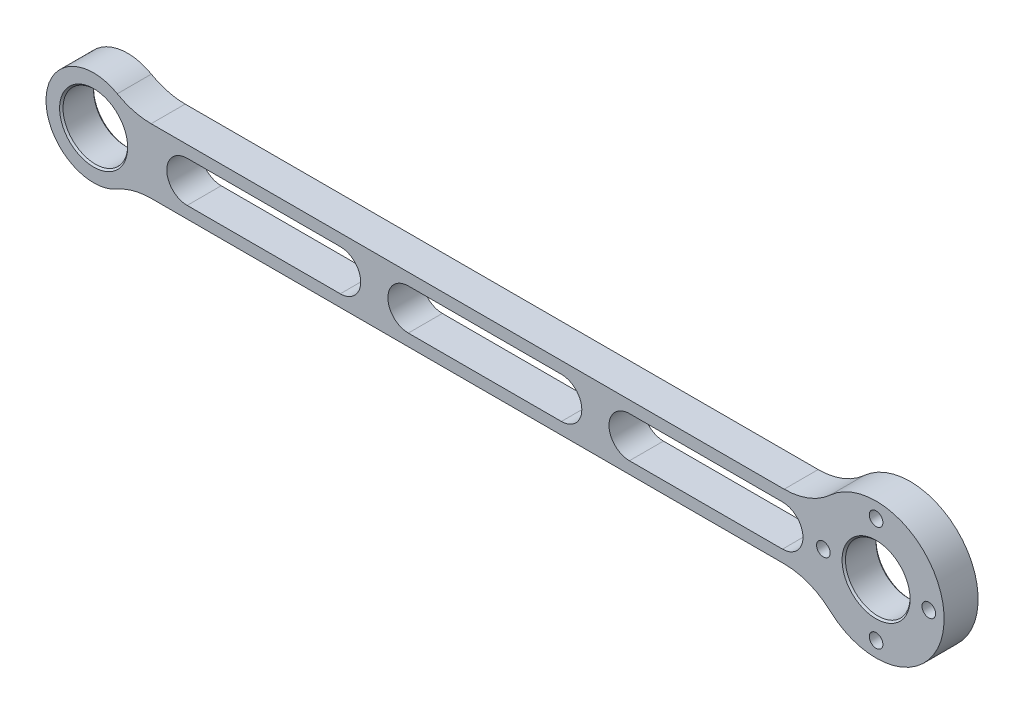
SolidWorks part; units mm, degrees
ref_plane "前视基准面" through (0, 0, 0) normal (0, 0, 1) x (1, 0, 0)
ref_plane "上视基准面" through (0, 0, 0) normal (0, 1, 0) x (1, 0, 0)
ref_plane "右视基准面" through (0, 0, 0) normal (1, 0, 0) x (0, 0, -1)
sketch "草图1" plane through (0, 0, 0) normal (0, 0, 1) x (1, 0, 0)
  line L0 (0, 0) -> (230, 0) construction
  line L1 (1.5589, 9.3712) -> (0, 9.5) construction
  line L2 (202.9861, -9.5) -> (20.8216, -9.5)
  line L4 (202.9861, 9.5) -> (21.6386, 9.5)
  line L6 (230, -9.5) -> (228.4411, -9.3712) construction
  line L7 (230, 9.5) -> (228.4411, 9.3712) construction
  line L8 (1.5589, -9.3712) -> (0, -9.5) construction
  line L9 (20.8216, -9.5) -> (16.9041, -9.5)
  line L10 (21.6386, 9.5) -> (16.9041, 9.5)
  circle A0 centre (0, 0) radius 9.5
  arc A1 (-0.2295, 13.9981) -> (3.4233, -13.575) centre (0, 0) ccw
  circle A2 centre (230, 0) radius 9.5
  arc A3 (214.8013, -13) -> (214.8013, 13) centre (230, 0) ccw
  arc A7 (6.9605, 12.1471) -> (6.9605, -12.1471) centre (0, 0) ccw
  arc A8 (6.9605, -12.1471) -> (16.9041, -9.5) centre (16.9041, -29.5) cw
  arc A9 (6.9605, 12.1471) -> (16.9041, 9.5) centre (16.9041, 29.5) ccw
  arc A10 (216.4931, -14.75) -> (216.4931, 14.75) centre (230, 0) ccw
  arc A11 (202.9861, -9.5) -> (216.4931, -14.75) centre (202.9861, -29.5) cw
  arc A12 (216.4931, 14.75) -> (202.9861, 9.5) centre (202.9861, 29.5) cw
  point P7 (115, 0)
  dimension "D1" = 19
  dimension "D2" = 28
  dimension "D3" = 20
  dimension "D4" = 19
  dimension "D5" = 20
  dimension "D8" = 20
  dimension "D6" = 9.5
  dimension "D7" = 9.5
extrude "凸台-拉伸2" add sketch "草图1" along normal blind 10 contours A1 L2 A3 L4 A2 A0 region at (127.347, 0, 0)
chamfer "倒角1" distance 0.5 angle 45 2 edges at (9.5, 0, 10) (9.5, 0, 0)
sketch "草图2" plane through (0, 0, 10) normal (0, 0, 1) x (1, 0, 0)
  line L0 (0, 0) -> (21.5, 0) construction
  line L1 (115, -1.5) -> (115, 9.5) construction
  line L2 (202.9861, 9.5) -> (16.9041, 9.5) construction
  line L3 (115, -1.5) -> (137.5, -6) construction
  line L4 (92.5, -6) -> (137.5, -6)
  line L6 (92.5, 6) -> (137.5, 6)
  line L8 (115, -1.5) -> (135.7692, 2.6538) construction
  line L10 (157.5, -6) -> (202.5, -6)
  line L12 (157.5, 6) -> (202.5, 6)
  line L16 (27.5, -6) -> (72.5, -6)
  line L18 (27.5, 6) -> (72.5, 6)
  line L20 (29.2308, -4.1538) -> (50, 0) construction
  line L21 (50, 0) -> (157.5, 0) construction
  line L22 (162, 0) -> (230, 0) construction
  arc A1 (27.5, 6) -> (27.5, -6) centre (27.5, 0) ccw
  arc A2 (92.5, 6) -> (92.5, -6) centre (92.5, 0) ccw
  arc A3 (137.5, -6) -> (137.5, 6) centre (137.5, 0) ccw
  arc A4 (157.5, 6) -> (157.5, -6) centre (157.5, 0) ccw
  arc A6 (72.5, -6) -> (72.5, 6) centre (72.5, 0) ccw
  arc A7 (202.5, -6) -> (202.5, 6) centre (202.5, 0) ccw
  point P12 (180, 0)
  point P17 (50, 0)
  dimension "D1" = 12
  dimension "D2" = 12
  dimension "D3" = 45
  dimension "D4" = 45
  dimension "D5" = 45
  dimension "D6" = 12
extrude "切除-拉伸1" cut sketch "草图2" against normal blind 10
sketch "草图3" plane through (0, 0, 10) normal (0, 0, 1) x (1, 0, 0)
  line L0 (230, 0) -> (243, 0) construction
  line L1 (230, 0) -> (236.5, 11.2583) construction
  line L2 (230, 0) -> (223.5, 11.2583) construction
  arc A8 (220.8385, 11.8771) -> (215.1333, 1.9956) centre (230, 0) ccw
  circle A9 centre (215, 0) radius 2
  circle A12 centre (245, 0) radius 2
  circle A13 centre (237.5, 12.9904) radius 2
  circle A14 centre (222.5, 12.9904) radius 2
  arc A15 (235.7051, 13.8727) -> (224.2949, 13.8727) centre (230, 0) ccw
  arc A16 (244.8667, 1.9956) -> (239.1615, 11.8771) centre (230, 0) ccw
  arc A17 (215.1333, -1.9956) -> (220.8385, -11.8771) centre (230, 0) ccw
  circle A18 centre (237.5, -12.9904) radius 2
  circle A19 centre (222.5, -12.9904) radius 2
  arc A20 (224.2949, -13.8727) -> (235.7051, -13.8727) centre (230, 0) ccw
  arc A21 (239.1615, -11.8771) -> (244.8667, -1.9956) centre (230, 0) ccw
  point P18 (230, 0)
  dimension "D1" = 60
  dimension "D2" = 60
extrude "切除-拉伸2" cut sketch "草图3" against normal blind 10 contours A12 | A14 | A13 region at (222.5, 12.9904, 10) region at (237.5, 12.9904, 10) region at (245, 0, 10)
chamfer "倒角2" distance 0.5 angle 45 1 edges at (239.5, 0, 10)
sketch "草图5" plane through (0, 0, 10) normal (0, 0, 1) x (1, 0, 0)
  line L0 (230, 0) -> (222.5, 12.9904) construction
  line L1 (230, 0) -> (221.3397, -5) construction
  arc A0 (215.1333, -1.9956) -> (220.8385, -11.8771) centre (230, 0) ccw
  circle A1 centre (245, 0) radius 2 construction
  circle A2 centre (237.5, 12.9904) radius 2 construction
  circle A3 centre (222.5, 12.9904) radius 2 construction
  circle A4 centre (245, 0) radius 2
  circle A5 centre (237.5, 12.9904) radius 2
  circle A6 centre (222.5, 12.9904) radius 2
  circle A7 centre (222.5, -12.9904) radius 2
  circle A8 centre (215, 0) radius 2
  circle A9 centre (230, 0) radius 10 construction
  circle A10 centre (237.5, -12.9904) radius 2
  arc A11 (224.2949, -13.8727) -> (235.7051, -13.8727) centre (230, 0) ccw
  arc A12 (239.1615, -11.8771) -> (215.1333, 1.9956) centre (230, 0) ccw
extrude "切除-拉伸3" cut sketch "草图5" against normal blind 10 contours A8 | A7 | A10 region at (215, 0, 10) region at (222.5, -12.9904, 10) region at (237.5, -12.9904, 10)
chamfer "倒角3" distance 0.5 angle 45 1 edges at (239.5, 0, 0)
ref_axis "基准轴1" through (230, 0, 9.5) along (0, 0, -1)
ref_axis "基准轴2" through (230, 0, 9.5) along (0, 0, -1)
ref_plane "基准面1" through (6.9353, 39.3323, 0) normal (0.1736, 0.9848, 0) x (0, 0, -1)
sketch "草图9" plane through (0, 0, 10) normal (0, 0, 1) x (1, 0, 0)
  circle A0 centre (215, 0) radius 2
  circle A1 centre (222.5, 12.9904) radius 2
  circle A2 centre (237.5, 12.9904) radius 2
  circle A3 centre (245, 0) radius 2
  circle A4 centre (237.5, -12.9904) radius 2
  circle A5 centre (222.5, -12.9904) radius 2
extrude "凸台-拉伸3" add sketch "草图9" against normal blind 10
sketch "草图10" plane through (0, 0, 10) normal (0, 0, 1) x (1, 0, 0)
  arc A0 (228.0042, 15.371) -> (214.629, 1.9958) centre (230, 0) ccw
  circle A1 centre (214.5, 0) radius 2
  arc A2 (214.629, -1.9958) -> (231.9958, 15.371) centre (230, 0) ccw
ref_axis "基准轴3" through (230, 0, 9.5) along (0, 0, -1)
extrude "切除-拉伸6" cut sketch "草图10" against normal blind 10 contours A1 region at (214.5, 0, 10)
pattern_circular "阵列(圆周)2" count 4 over 360 about axis through (230, 0, 9.5) along (0, 0, -1) of "切除-拉伸6"
